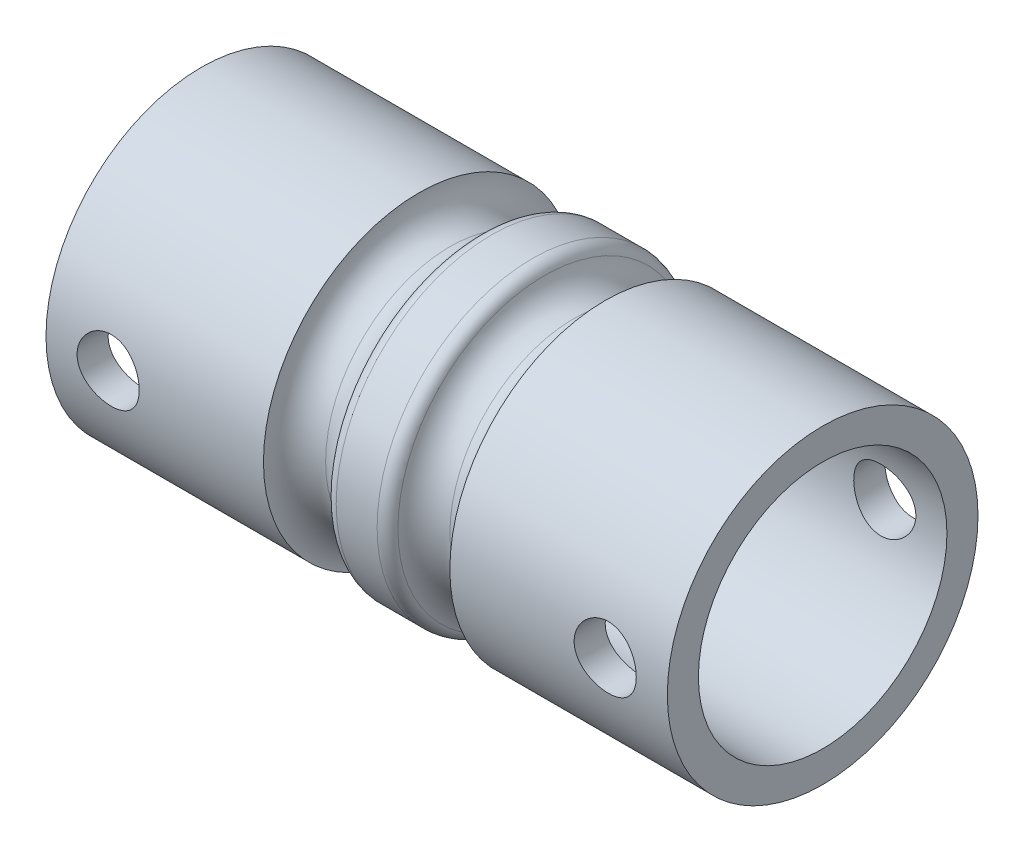
SolidWorks part; units mm, degrees
material "5052-H32"
ref_plane "Front Plane" through (0, 0, 0) normal (0, 0, 1) x (1, 0, 0)
ref_plane "Top Plane" through (0, 0, 0) normal (0, 1, 0) x (1, 0, 0)
ref_plane "Right Plane" through (0, 0, 0) normal (1, 0, 0) x (0, 0, -1)
sketch "Sketch1" plane through (0, 0, 0) normal (1, 0, 0) x (0, 0, -1)
  circle A0 centre (0, 0) radius 12.5
  circle A1 centre (0, 0) radius 10
  dimension "D1" = 20
  dimension "D2" = 25
extrude "Boss-Extrude1" add sketch "Sketch1" along normal blind 50
sketch "Sketch2" plane through (0, 0, 0) normal (0, 0, 1) x (1, 0, 0)
  line L0 (50, 12.5) -> (0, 12.5) construction
  line L1 (0, 12.5) -> (0, -12.5) construction
  line L2 (50, -12.5) -> (50, 12.5) construction
  line L3 (-6.3598, 0) -> (62.2711, 0) construction
  circle A0 centre (20, 12.5) radius 2.5
  circle A1 centre (30, 12.5) radius 2.5
  dimension "D1" = 5
  dimension "D2" = 5
  dimension "D3" = 20
  dimension "D4" = 20
revolve "Cut-Revolve1" cut sketch "Sketch2" angle 360 about L3
fillet "Fillet1" radius 1 2 edges at (27.5, 0, -12.5) (22.5, 0, 12.5)
sketch "Sketch3" plane through (0, 0, 0) normal (0, 0, 1) x (1, 0, 0)
  line L0 (0, 12.5) -> (0, -12.5) construction
  line L1 (50, -12.5) -> (50, 12.5) construction
  circle A0 centre (5, 0) radius 2.5
  circle A1 centre (45, 0) radius 2.5
  point P8 (0, 0)
  point P9 (0, 0)
  dimension "D1" = 5
  dimension "D2" = 5
  dimension "D3" = 5
  dimension "D4" = 5
extrude "Cut-Extrude1" cut sketch "Sketch3" against normal through all and the other way through all
